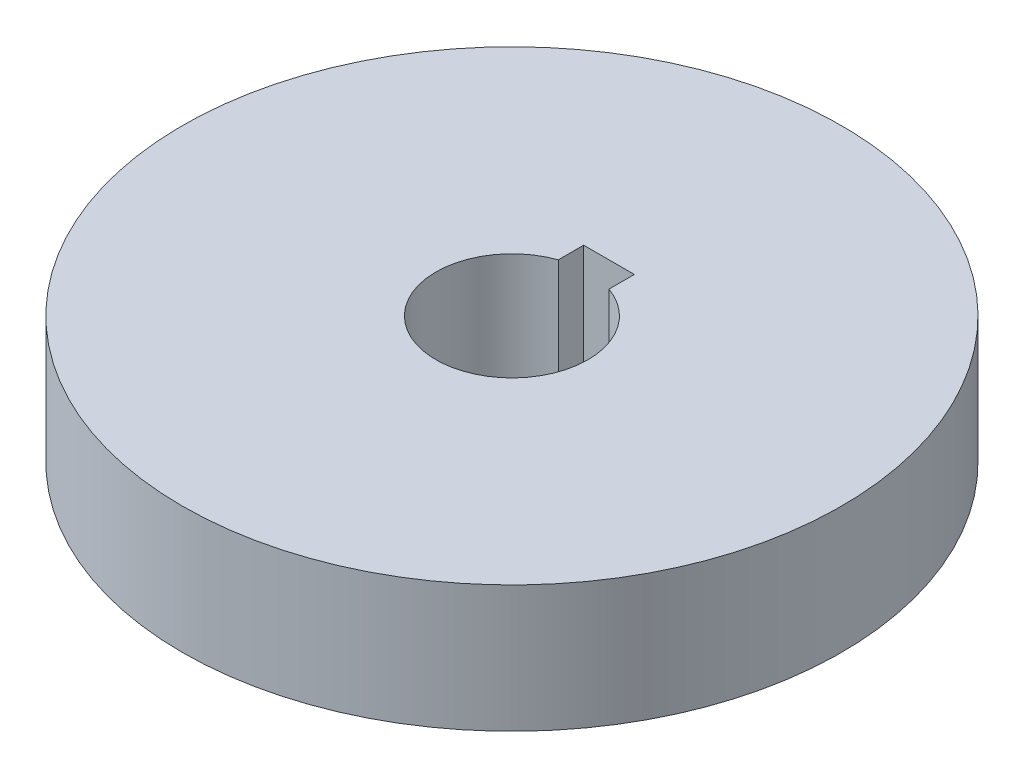
SolidWorks part; units mm, degrees
material "2024-T4"
ref_plane "Front Plane" through (0, 0, 0) normal (0, 0, 1) x (1, 0, 0)
ref_plane "Top Plane" through (0, 0, 0) normal (0, 1, 0) x (1, 0, 0)
ref_plane "Right Plane" through (0, 0, 0) normal (1, 0, 0) x (0, 0, -1)
sketch "Sketch1" plane through (0, 0, 0) normal (0, 1, 0) x (1, 0, 0)
  circle A0 centre (0, 0) radius 26
  circle A1 centre (0, 0) radius 6
  dimension "D1" = 12
  dimension "D2" = 52
extrude "Boss-Extrude1" add sketch "Sketch1" along normal blind 10
sketch "Sketch2" plane through (0, 10, 0) normal (0, 1, 0) x (1, 0, 0)
  line L0 (0, 0) -> (0, 6) construction
  line L1 (0, 6) -> (0, 7.6569) construction
  line L2 (2, 7.6569) -> (-2, 7.6569)
  line L3 (-2, 7.6569) -> (-2, 5.6569)
  line L4 (2, 7.6569) -> (2, 5.6569)
  circle A0 centre (0, 0) radius 6 construction
  circle A1 centre (0, 0) radius 6
  circle M6 centre (0, 0) radius 6
  dimension "D1" = 2
extrude "Cut-Extrude1" cut sketch "Sketch2" against normal through all contours L4 L2 L3 M6 region at (0, 10, -6.769)
equation "\"shaft-diameter\" =20mm"
equation "\"key-length\"=12mm"
equation "\"key-width\"=4mm"
equation "\"flippershaft-wormgear-diameter\" = 35mm"
equation "\"shaft-ring-groove-depth\"=0.5mm"
equation "\"shaft-ring-groove-width\" = 1.3mm"
equation "\"mini-shaft-diameter\" = 12mm"
equation "\"D1@Sketch1\"=\"mini-shaft-diameter\""
equation "\"D2@Sketch2\"=\"key-width\"/2"
